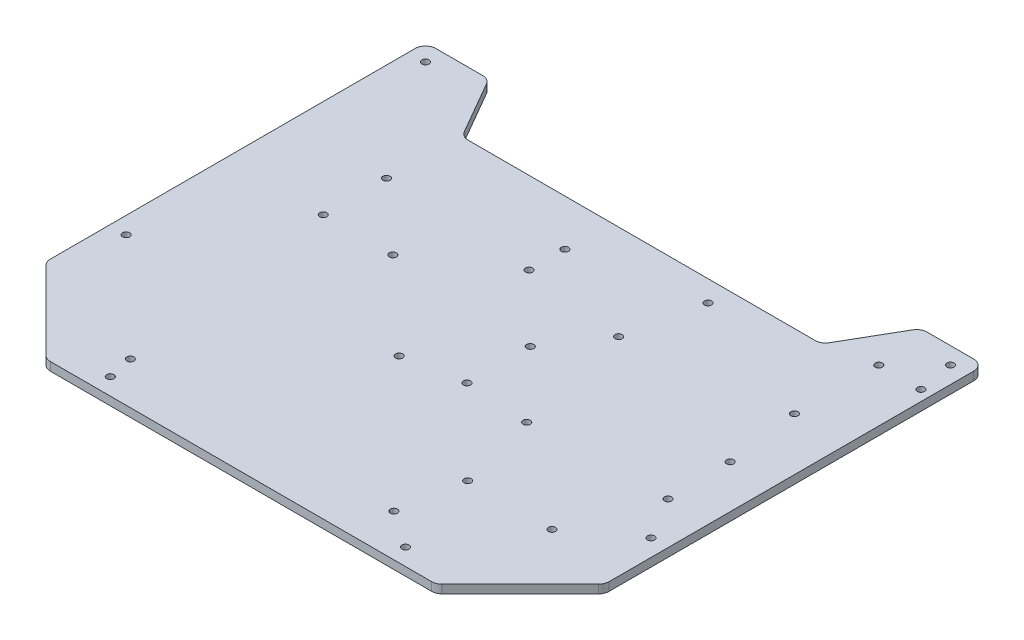
SolidWorks part; units mm, degrees
material "Acier non allié"
ref_plane "Front" through (0, 0, 0) normal (0, 0, 1) x (1, 0, 0)
ref_plane "Top" through (0, 0, 0) normal (0, 1, 0) x (1, 0, 0)
ref_plane "Right" through (0, 0, 0) normal (1, 0, 0) x (0, 0, -1)
sketch "Main scetch" plane through (0, 0, 0) normal (0, 1, 0) x (1, 0, 0)
  line L1 (0, 0) -> (132.5, 0) construction
  line L2 (0, 0) -> (0, 220) construction
  line L3 (0, 220) -> (132.5, 220) construction
  line L4 (132.5, 0) -> (132.5, 220) construction
  line L13 (-92.5, 0) -> (92.5, 0)
  line L14 (92.5, 0) -> (132.5, 40)
  line L15 (132.5, 40) -> (132.5, 220)
  line L16 (132.5, 220) -> (102.5, 220)
  line L17 (102.5, 220) -> (85.1795, 190)
  line L18 (85.1795, 190) -> (-85.1795, 190)
  line L19 (-102.5, 220) -> (-85.1795, 190)
  line L20 (-132.5, 220) -> (-102.5, 220)
  line L21 (-132.5, 40) -> (-132.5, 220)
  line L22 (-92.5, 0) -> (-132.5, 40)
  point P11 (0, 190)
  dimension "132.5" = 132.5
  dimension "D2" = 220
  dimension "D1" = 40
  dimension "D3" = 40
  dimension "D4" = 30
  dimension "D5" = 60
  dimension "D6" = 30
extrude "Main extrusion" add sketch "Main scetch" along normal blind 4
fillet "Congé1" radius 5 10 edges at (-132.5, 2, -40) (-92.5, 2, 0) (92.5, 2, 0) (132.5, 2, -40) (132.5, 2, -220) (102.5, 2, -220) (85.1795, 2, -190) (-85.1795, 2, -190) (-102.5, 2, -220) (-132.5, 2, -220)
sketch "Esquisse1" plane through (0, 4, 0) normal (0, 1, 0) x (1, 0, 0)
  line L0 (0, 0) -> (0, 218.5516) construction
  line L1 (132.5, 42.0711) -> (132.5, 215) construction
  line L2 (127.5, 220) -> (105.3868, 220) construction
  line L3 (-90.4289, 0) -> (90.4289, 0) construction
  circle A0 centre (70, 8) radius 1
  circle A1 centre (124.5, 70) radius 1
  circle A2 centre (124.5, 212) radius 1
  circle A3 centre (-124.5, 212) radius 1
  circle A4 centre (-124.5, 70) radius 1
  circle A5 centre (-70, 8) radius 1
  dimension "D1" = 2
  dimension "D2" = 2
  dimension "D3" = 2
  dimension "D4" = 8
  dimension "D5" = 8
  dimension "D6" = 8
  dimension "D7" = 8
  dimension "D8" = 70
  dimension "D9" = 70
extrude "Enlèv. mat.-Extru.1" cut sketch "Esquisse1" against normal through all
hole_wizard "Dégagement M31" positions "Esquisse2" profile "Esquisse3" hole size "M3" standard "ISO" end condition through all
sketch "Esquisse2" plane through (0, 4, 0) normal (0, 1, 0) x (1, 0, 0)
  point P0 (-124.5, 212)
  point P3 (-124.5, 70)
  point P6 (-70, 8)
  point P9 (70, 8)
  point P12 (124.5, 70)
  point P15 (124.5, 212)
sketch "Esquisse3" plane through (-124.5, 4, -212) normal (1, 0, 0) x (0, 0, 1)
  line L0 (0, 0) -> (0, 4)
  line L1 (0, 4) -> (1.7, 4)
  line L2 (1.7, 4) -> (1.7, 0)
  line L5 (1.7, 0) -> (0, 0)
  line L11 (0, -6.35) -> (0, 107.95) construction
  dimension "Diamètre du perçage jusqu'au prochain" = 3.4
  dimension "Profondeur du perçage jusqu'au prochain" = 4
sketch "Esquisse4" plane through (0, 4, 0) normal (0, 1, 0) x (1, 0, 0)
  line L0 (-132.5, 215) -> (-132.5, 42.0711) construction
  line L1 (-105.3868, 220) -> (-127.5, 220) construction
  line L2 (82.2927, 190) -> (-82.2927, 190) construction
  line L3 (132.5, 42.0711) -> (132.5, 215) construction
  line L4 (-90.4289, 0) -> (90.4289, 0) construction
  line L5 (127.5, 220) -> (105.3868, 220) construction
  circle A0 centre (-86, 125) radius 1
  circle A1 centre (-86, 155) radius 1
  circle A2 centre (-53, 125) radius 1
  circle A3 centre (-14.5, 151.1) radius 1
  circle A4 centre (-14.5, 168.1) radius 1
  circle A5 centre (41.5, 180) radius 1
  circle A6 centre (34.12, 145) radius 1
  circle A7 centre (107.5, 155) radius 1
  circle A8 centre (127.5, 195) radius 1
  circle A9 centre (112, 120) radius 1
  circle A10 centre (112.5, 90) radius 1
  circle A11 centre (17.2, 120) radius 1
  circle A12 centre (17.2, 90) radius 1
  circle A13 centre (47.5, 88) radius 1
  circle A14 centre (57.5, 50) radius 1
  circle A15 centre (97.5, 50) radius 1
  circle A16 centre (52.5, 20) radius 1
  circle A17 centre (-10, 85) radius 1
  circle A18 centre (-72.5, 20) radius 1
  circle A19 centre (107.5, 195) radius 1
  dimension "D1" = 2
  dimension "D4" = 2
  dimension "D6" = 2
  dimension "D8" = 2
  dimension "D11" = 2
  dimension "D13" = 2
  dimension "D16" = 2
  dimension "D19" = 2
  dimension "D24" = 2
  dimension "D25" = 2
  dimension "D28" = 2
  dimension "D30" = 2
  dimension "D32" = 2
  dimension "D36" = 2
  dimension "D37" = 2
  dimension "D40" = 2
  dimension "D48" = 2
  dimension "D49" = 2
  dimension "D50" = 2
  dimension "D52" = 2
  dimension "D2" = 46.5
  dimension "D3" = 95
  dimension "D5" = 65
  dimension "D7" = 79.5
  dimension "D9" = 38.9
  dimension "D10" = 118
  dimension "D12" = 21.9
  dimension "D14" = 174
  dimension "D15" = 10
  dimension "D17" = 166.62
  dimension "D18" = 45
  dimension "D20" = 25
  dimension "D21" = 65
  dimension "D22" = 5
  dimension "D23" = 25
  dimension "D26" = 20.5
  dimension "D27" = 100
  dimension "D29" = 30
  dimension "D31" = 115.3
  dimension "D33" = 115.3
  dimension "D34" = 132
  dimension "D35" = 85
  dimension "D38" = 50
  dimension "D39" = 75
  dimension "D41" = 35
  dimension "D42" = 80
  dimension "D43" = 20
  dimension "D44" = 20
  dimension "D45" = 205
  dimension "D46" = 85
  dimension "D47" = 142.5
  dimension "D51" = 25
  dimension "D53" = 25
extrude "Enlèv. mat.-Extru.2" cut sketch "Esquisse4" against normal through all
hole_wizard "Dégagement M32" positions "Esquisse5" profile "Esquisse6" hole size "M3" standard "ISO" end condition through all
sketch "Esquisse5" plane through (0, 4, 0) normal (0, 1, 0) x (1, 0, 0)
  point P0 (-86, 155)
  point P3 (-86, 125)
  point P6 (-53, 125)
  point P9 (17.2, 120)
  point P12 (-14.5, 151.1)
  point P15 (-14.5, 168.1)
  point P18 (34.12, 145)
  point P21 (41.5, 180)
  point P24 (107.5, 155)
  point P27 (127.5, 195)
  point P30 (112, 120)
  point P33 (112.5, 90)
  point P36 (47.5, 88)
  point P39 (17.2, 90)
  point P42 (57.5, 50)
  point P45 (97.5, 50)
  point P48 (-10, 85)
  point P51 (-72.5, 20)
  point P54 (52.5, 20)
  point P57 (107.5, 195)
sketch "Esquisse6" plane through (-86, 4, -155) normal (1, 0, 0) x (0, 0, 1)
  line L0 (0, 0) -> (0, 4)
  line L1 (0, 4) -> (1.7, 4)
  line L2 (1.7, 4) -> (1.7, 0)
  line L5 (1.7, 0) -> (0, 0)
  line L11 (0, -6.35) -> (0, 107.95) construction
  dimension "Diamètre du perçage jusqu'au prochain" = 3.4
  dimension "Profondeur du perçage jusqu'au prochain" = 4
equation "\"WIDTH\"= 300mm'Total width of the robot"
equation "\"LENGTH\"= 220mm'Total length of the robot"
equation "\"D2@Main scetch\" = \"LENGTH\""
equation "\"CUT_DEPTH\"= 45mm'Depth of the cut on the edges of the plate"
equation "\"Plate_th\"= 3mm'Thickness of the plate"
equation "\"D1\"= \"Plate_th\""
equation "\"D47@Esquisse4\"=(80+205)/2"
